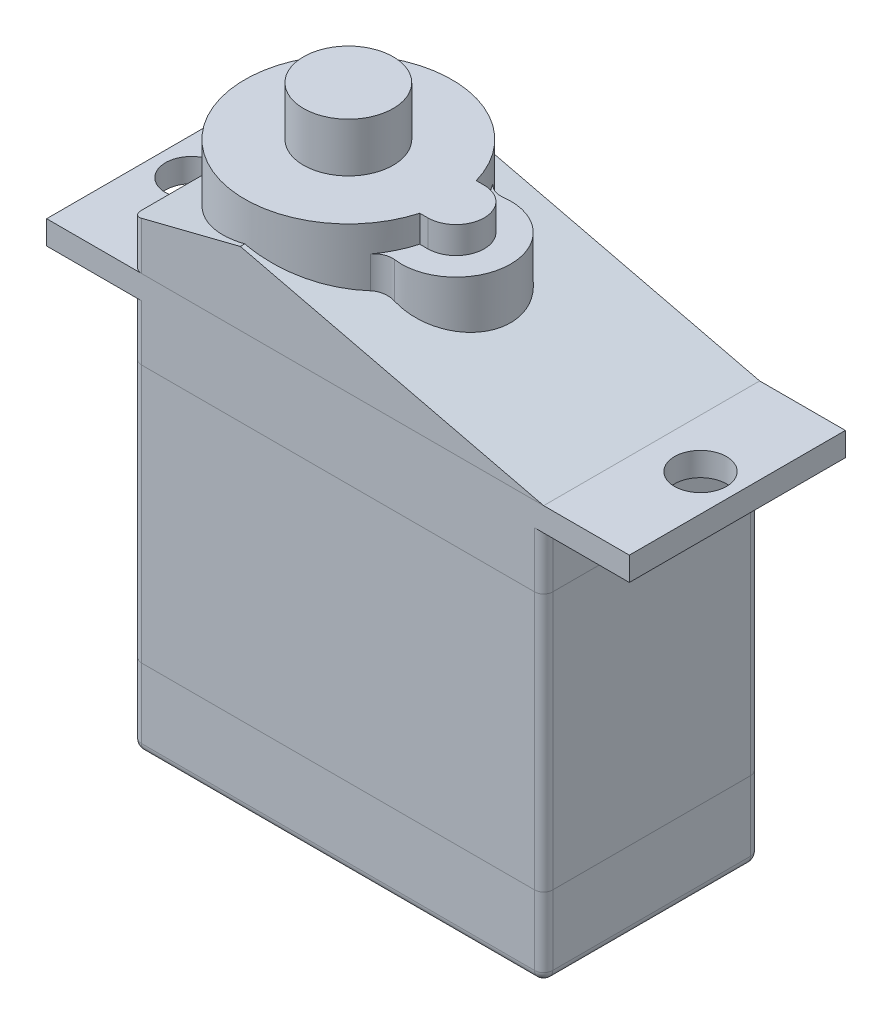
SolidWorks part; units mm, degrees
ref_plane "Front Plane" through (0, 0, 0) normal (0, 0, 1) x (1, 0, 0)
ref_plane "Top Plane" through (0, 0, 0) normal (0, 1, 0) x (1, 0, 0)
ref_plane "Right Plane" through (0, 0, 0) normal (1, 0, 0) x (0, 0, -1)
sketch "Sketch1" plane through (0, 0, 0) normal (0, 1, 0) x (1, 0, 0)
  line L1 (0, 0) -> (22.9489, 0)
  line L2 (0, 0) -> (0, 12.0523)
  line L3 (0, 12.0523) -> (22.9489, 12.0523)
  line L4 (22.9489, 0) -> (22.9489, 12.0523)
  dimension "D1" = 22.9489
  dimension "D2" = 12.0523
extrude "Boss-Extrude1" add sketch "Sketch1" along normal blind 4.4
sketch "Sketch2" plane through (0, 4.4, 0) normal (0, 1, 0) x (1, 0, 0)
  line L1 (0, 0) -> (22.9489, 0)
  line L2 (0, 0) -> (0, 12.0523)
  line L3 (0, 12.0523) -> (22.9489, 12.0523)
  line L4 (22.9489, 0) -> (22.9489, 12.0523)
extrude "Boss-Extrude4" add sketch "Sketch2" along normal blind 14.4 separate body
sketch "Sketch5" plane through (0, 18.8, 0) normal (0, 1, 0) x (1, 0, 0)
  line L1 (0, 0) -> (22.9489, 0)
  line L2 (0, 0) -> (0, 12.0523)
  line L3 (0, 12.0523) -> (22.9489, 12.0523)
  line L4 (22.9489, 0) -> (22.9489, 12.0523)
extrude "Boss-Extrude6" add sketch "Sketch5" along normal blind 4.4196 separate body
sketch "Sketch7" plane through (0, 0, 0) normal (-1, 0, 0) x (0, 0, 1)
  line L1 (-12.0523, 21.8988) -> (0, 21.8988)
  line L2 (-12.0523, 21.8988) -> (-12.0523, 23.2196)
  line L3 (-12.0523, 23.2196) -> (0, 23.2196)
  line L4 (0, 21.8988) -> (0, 23.2196)
  line L5 (0, 23.2196) -> (0, 18.8) construction
  line L7 (-12.0523, 23.2196) -> (0, 23.2196) construction
  dimension "D1" = 1.3208
extrude "Boss-Extrude9" add sketch "Sketch7" along normal blind 4.7816
ref_plane "Plane1" through (0, 0, -6.0261) normal (0, 0, -1) x (-1, 0, 0)
sketch "Sketch10" plane through (0, 23.2196, 0) normal (0, 1, 0) x (1, 0, 0)
  line L0 (-4.7816, 12.0523) -> (-4.7816, 0) construction
  line L1 (-4.7816, 6.0261) -> (-2.7256, 6.0261) construction
  line L2 (-4.7815, 7.0193) -> (-4.7815, 5.033) construction
  line L4 (22.9489, 12.0523) -> (-4.7816, 12.0523) construction
  line L5 (11.4744, 12) -> (11.4744, 0) construction
  line L6 (0, 0) -> (22.9489, 0) construction
  circle A0 centre (-2.7256, 6.0261) radius 1.4478
  point P17 (11.4744, 0)
  dimension "D1" = 2.8956
  dimension "D2" = 14.2
extrude "Cut-Extrude1" cut sketch "Sketch10" against normal up to next (1.3208 mm away)
ref_plane "Plane2" through (11.4744, 0, 0) normal (-1, 0, 0) x (0, 0, 1)
mirror "Mirror1" about plane through (11.4744, 0, 0) normal (-1, 0, 0) of "Cut-Extrude1", "Boss-Extrude9"
sketch "Sketch11" plane through (0, 23.2196, 0) normal (0, 1, 0) x (1, 0, 0)
  line L0 (0, 6.0261) -> (22.9489, 6.0261) construction
  line L1 (0, 12.0523) -> (0, 0) construction
  line L2 (22.9489, 0) -> (22.9489, 12.0523) construction
  line L3 (0, 12.0523) -> (6.0262, 6.0261) construction
  line L4 (27.7304, 12.0523) -> (-4.7816, 12.0523) construction
  arc A0 (10.6794, 9.4523) -> (10.6794, 2.6) centre (6.0262, 6.0261) ccw
  arc A1 (11.6315, 9.0476) -> (11.6315, 3.0047) centre (12.0333, 6.0261) cw
  arc A2 (10.6794, 2.6) -> (11.6315, 3.0047) centre (11.4975, 1.9976) cw
  arc A3 (10.6794, 9.4523) -> (11.6315, 9.0476) centre (11.4975, 10.0547) ccw
  point P13 (0.2477, 6.0261)
  point P15 (15.0813, 6.0261)
  point P16 (11.0357, 3.146)
  point P19 (11.0357, 8.9063)
  dimension "D2" = 11.557
  dimension "D3" = 3.048
  dimension "D5" = 1.016
  dimension "D1" = 45
  dimension "D4" = 14.8336
extrude "Boss-Extrude10" add sketch "Sketch11" along normal blind 4.7244 separate body
fillet "Fillet1" radius 0.508 4 edges at (0, 11.6, -12.0523) (0, 11.6, 0) (22.9489, 11.6, 0) (22.9489, 11.6, -12.0523)
sketch "Sketch12" plane through (0, 27.944, 0) normal (0, 1, 0) x (1, 0, 0)
  line L0 (12.0333, 4.4513) -> (11.5859, 4.4513)
  line L1 (12.0333, 7.6009) -> (11.5859, 7.6009)
  arc A0 (10.6794, 9.4523) -> (10.6794, 2.6) centre (6.0262, 6.0261) ccw construction
  arc A1 (10.6794, 9.4523) -> (10.6794, 2.6) centre (6.0262, 6.0261) ccw construction
  arc A3 (11.6315, 3.0047) -> (11.6315, 9.0476) centre (12.0333, 6.0261) ccw construction
  arc A4 (11.6315, 3.0047) -> (11.6315, 9.0476) centre (12.0333, 6.0261) ccw construction
  arc A5 (12.0333, 4.4513) -> (12.0333, 7.6009) centre (12.0333, 6.0261) ccw
  arc A6 (11.5859, 4.4513) -> (11.5859, 7.6009) centre (6.0262, 6.0261) cw
  dimension "D1" = 1.5748
  dimension "D2" = 5.7785
extrude "Boss-Extrude11" add sketch "Sketch12" along normal blind 1.4986
sketch "Sketch13" plane through (0, 29.4426, 0) normal (0, 1, 0) x (1, 0, 0)
  arc A0 (11.5859, 7.601) -> (11.5859, 4.4513) centre (6.0262, 6.0261) ccw construction
  arc A1 (11.5859, 7.601) -> (11.5859, 4.4513) centre (6.0262, 6.0261) ccw construction
  circle A2 centre (6.0262, 6.0261) radius 2.5019
  dimension "D1" = 5.0038
extrude "Boss-Extrude12" add sketch "Sketch13" along normal blind 2.7432
sketch "Sketch14" plane through (0, 0, 0) normal (-1, 0, 0) x (0, 0, 1)
  line L0 (-12.0523, 0) -> (0, 0) construction
  line L1 (-9.4679, 0) -> (-2.5844, 0)
  line L2 (-9.4679, 0) -> (-9.4679, 4.4)
  line L3 (-9.4679, 4.4) -> (-2.5845, 4.4)
  line L4 (-2.5844, 0) -> (-2.5845, 4.4)
  line L6 (-12.0523, 4.4) -> (0, 4.4) construction
  point P9 (-6.0261, 0)
  dimension "D1" = 6.8834
extrude "Boss-Extrude14" add sketch "Sketch14" along normal blind 0.4064
sketch "Sketch15" plane through (-0.4064, 0, 0) normal (-1, 0, 0) x (0, 0, 1)
  line L0 (-9.4679, 1.778) -> (-2.5844, 1.778) construction
  line L1 (-9.4679, 4.4) -> (-9.4679, 0) construction
  line L2 (-2.5844, 0) -> (-2.5845, 4.4) construction
  line L3 (-9.4679, 0) -> (-2.5844, 0) construction
  circle A0 centre (-6.0261, 1.778) radius 0.5715
  circle A1 centre (-4.8831, 1.778) radius 0.5715
  circle A2 centre (-7.1691, 1.778) radius 0.5715
  dimension "D1" = 1.143
  dimension "D2" = 1.778
extrude "Boss-Extrude15" add sketch "Sketch15" along normal blind 1.27 separate body contours A0 | A1 | A2
fillet "Fillet4" radius 0.508 12 edges at (-0.4064, 0, -6.0261) (11.4744, 0, 0) (22.9489, 0, -6.0261) (11.4744, 0, -12.0523) (0, 2.2, 0) (22.9489, 2.2, 0) (22.9489, 2.2, -12.0523) (0, 2.2, -12.0523)
sketch3d "3DSketch1"
  line L0 (6.0262, 32.1858, -6.0261) -> (6.0262, 32.1858, -12.0523) construction
  line L1 (6.0262, 32.1858, -6.0261) -> (6.0262, 29.4426, -6.0261) construction
  line L2 (6.0262, 23.2196, -12.0523) -> (6.0262, 32.1858, -12.0523) construction
  line L3 (27.7304, 23.2196, -12.0523) -> (-4.7816, 23.2196, -12.0523) construction
  line L4 (6.0262, 27.2836, -12.0523) -> (22.9489, 23.2196, -12.0523)
  line L5 (22.9489, 23.2196, -12.0523) -> (22.9489, 21.8988, -12.0523) construction
  line L6 (0, 23.2196, -12.0523) -> (0, 25.7596, -12.0523)
  line L7 (6.0262, 27.2836, -12.0523) -> (0, 25.7596, -12.0523)
  line L8 (0, 23.2196, -12.0523) -> (22.9489, 23.2196, -12.0523)
  line L9 (0, 23.2196, -12.0523) -> (0, 21.8988, -12.0523) construction
  point P14 (0, 23.2196, -12.0523)
  dimension "D1" = 4.064
  dimension "D2" = 2.54
extrude "Boss-Extrude16" add sketch "3DSketch1" along direction (0, 0, -1) on the side against the normal through all contours L8 L4 L7 L6
fillet "Fillet5" radius 0.508 6 edges
